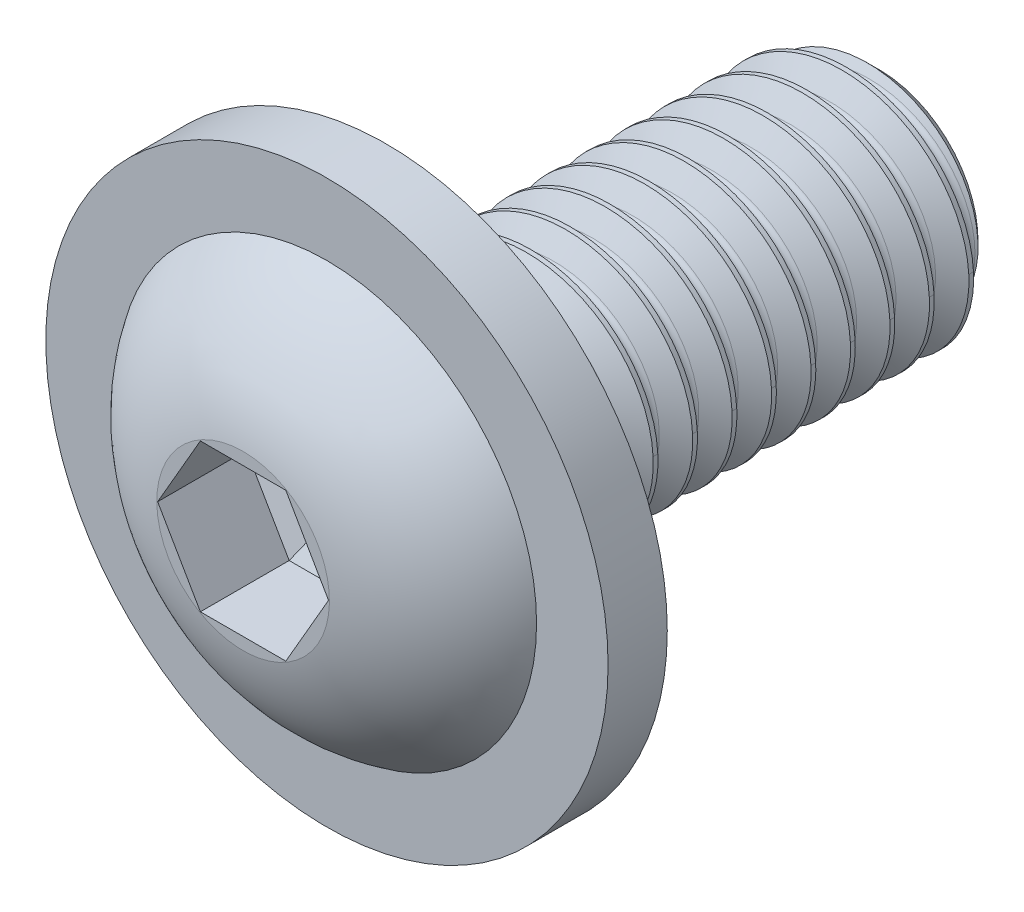
SolidWorks part; units mm, degrees
material "1.4031(X39Cr13)"
ref_plane "Ebene vorne" through (0, 0, 0) normal (0, 0, 1) x (1, 0, 0)
ref_plane "Ebene oben" through (0, 0, 0) normal (0, 1, 0) x (1, 0, 0)
ref_plane "Ebene rechts" through (0, 0, 0) normal (1, 0, 0) x (0, 0, -1)
sketch "Skizze1" plane through (0, 0, 0) normal (0, 0, 1) x (1, 0, 0)
  circle A0 centre (0, 0) radius 5.7
  dimension "D1" = 11.4
extrude "Aufsatz-Linear austragen1" add sketch "Skizze1" along normal blind 1.2
sketch "Skizze2" plane through (0, 0, 0) normal (1, 0, 0) x (0, 0, -1)
  line L0 (-1.2, 5.7) -> (-1.2, -5.7) construction
  line L1 (-1.2, 0) -> (-2.9, 0) construction
  line L2 (-2.9, 1.75) -> (-2.9, -1.75)
  line L3 (0, -5.7) -> (0, 5.7) construction
  line L4 (-1.2, 4.25) -> (-1.2, 0)
  line L5 (-1.2, 0) -> (-2.9, 0)
  arc A0 (-1.2, 4.25) -> (-2.9, 1.75) centre (0.8, 1.062) ccw
  arc A1 (-1.2, -4.25) -> (-2.9, -1.75) centre (0.8, -1.062) cw
  dimension "D1" = 3.5
  dimension "D2" = 2.9
  dimension "D3" = 8.5
  dimension "D4" = 2
revolve "Rotation1" add sketch "Skizze2" angle 360 about L5 region at (0, 1.7533, 1.957)
sketch "Skizze4" plane through (0, 0, 2.9) normal (0, 0, 1) x (1, 0, 0)
  line L1 (-0.866, -1.5) -> (0.866, -1.5)
  line L2 (0.866, -1.5) -> (1.7321, 0)
  line L3 (1.7321, 0) -> (0.866, 1.5)
  line L4 (0.866, 1.5) -> (-0.866, 1.5)
  line L5 (-0.866, 1.5) -> (-1.7321, 0)
  line L6 (-1.7321, 0) -> (-0.866, -1.5)
  circle A0 centre (0, 0) radius 1.5 construction
  circle A1 centre (0, 0) radius 1.75 construction
  dimension "D1" = 3
extrude "Schnitt-Linear austragen1" cut sketch "Skizze4" against normal blind 2.4
chamfer "Fase1" distance 0.6 angle 65 6 edges at (-1.299, -0.75, 0.5) (0, -1.5, 0.5) (1.299, -0.75, 0.5) (1.299, 0.75, 0.5) (-1.299, 0.75, 0.5) (0, 1.5, 0.5) first distance on face at (-1.299, -0.75, 1.7) first distance on face at (0, -1.5, 1.7) first distance on face at (1.299, -0.75, 1.7) first distance on face at (1.299, 0.75, 1.7) first distance on face at (-1.299, 0.75, 1.7) first distance on face at (0, 1.5, 1.7)
sketch "Skizze5" plane through (0, 0, 0) normal (0, 0, -1) x (-1, 0, 0)
  circle A0 centre (0, 0) radius 2.5
  dimension "D1" = 5
extrude "Aufsatz-Linear austragen2" add sketch "Skizze5" along normal blind 10
fillet "Verrundung1" radius 0.75 1 edges at (-2.5, 0, 0)
chamfer "Fase2" distance 0.5 angle 45 1 edges at (-2.5, 0, -10)
sketch "Skizze6" plane through (0, 0, -10) normal (0, 0, -1) x (-1, 0, 0)
  circle A0 centre (0, 0) radius 2.5 construction
  circle A1 centre (0, 0) radius 2.5
curve "Spirale/Helix1" pitch 0.8 height 9 radius 2.5 centre (0, 0, -10) axis (0, 0, 1) start towards (-1, 0, 0)
sketch "Skizze7" plane through (0, 0, 0) normal (0, 1, 0) x (1, 0, 0)
  line L0 (-2.5, 9.8078) -> (-2.07, 10.0561)
  line L1 (-2.07, 10.2639) -> (-2.5, 10.5122)
  line L2 (-2.5, 10.5122) -> (-2.5, 9.8078)
  line L3 (-2.5, 9.5) -> (-2.5, 0.75) construction
  line L4 (0, 10) -> (0, 12.099) construction
  line L5 (2, 10) -> (-2, 10) construction
  line L6 (-2.5, 9.5) -> (2.5, 9.5) construction
  arc A0 (-2.07, 10.0561) -> (-2.07, 10.2639) centre (-2.13, 10.16) ccw
  dimension "D1" = 0.12
  dimension "D2" = 2.01
  dimension "D3" = 60
  dimension "D4" = 0.66
sweep "Schnitt-Austragung1" cut profiles "Skizze7" path "Spirale/Helix1" align with end faces yes
extrude "Aufsatz-Linear austragen3" add sketch "Skizze6<2>" along normal blind 2 from surface starting at face at (3.25, 0, 0)
sketch "Skizze6<2>" plane through (0, 0, -10) normal (0, 0, -1) x (-1, 0, 0) same geometry as "Skizze6"
